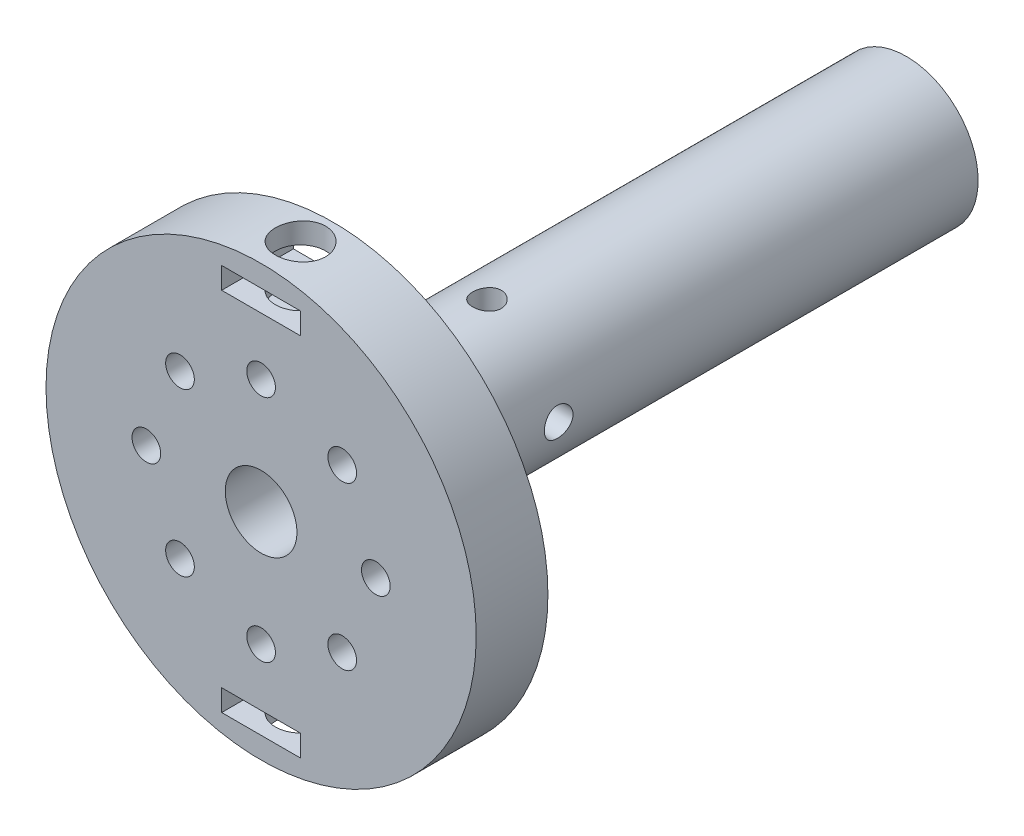
SolidWorks part; units mm, degrees
ref_plane "Front Plane" through (0, 0, 0) normal (0, 0, 1) x (1, 0, 0)
ref_plane "Top Plane" through (0, 0, 0) normal (0, 1, 0) x (1, 0, 0)
ref_plane "Right Plane" through (0, 0, 0) normal (1, 0, 0) x (0, 0, -1)
sketch "Sketch1" plane through (0, 0, 0) normal (0, 0, 1) x (1, 0, 0)
  circle A0 centre (0, 0) radius 30
  dimension "D1" = 60
extrude "Boss-Extrude1" add sketch "Sketch1" along normal blind 10
sketch "Sketch2" plane through (0, 0, 0) normal (0, 0, -1) x (-1, 0, 0)
  circle A0 centre (0, 0) radius 10
  dimension "D1" = 20
extrude "Boss-Extrude2" add sketch "Sketch2" along normal blind 80
extrude "Boss-Extrude3" add sketch "Sketch2<2>" along normal blind 20
sketch "Sketch2<2>" plane through (0, 0, 0) normal (0, 0, -1) x (-1, 0, 0) same geometry as "Sketch2"
sketch "Sketch5" plane through (0, 0, -80) normal (0, 0, -1) x (-1, 0, 0)
  circle A0 centre (0, 0) radius 5
  dimension "D1" = 10
extrude "Cut-Extrude1" cut sketch "Sketch5" against normal through all
sketch "Sketch6" plane through (0, 0, 0) normal (0, 1, 0) x (1, 0, 0)
  line L1 (30, 0) -> (-30, 0) construction
  circle A0 centre (0, 21.5) radius 2
  dimension "D1" = 4
  dimension "D2" = 21.5
extrude "Cut-Extrude2" cut sketch "Sketch6" against normal through all both and the other way through all
pattern_circular "CirPattern1" count 2 over 90 about axis through (0, 0, -80) along (0, 0, 1) of "Cut-Extrude2"
sketch "Sketch7" plane through (0, 0, 10) normal (0, 0, 1) x (1, 0, 0)
  circle A0 centre (0, 16) radius 2
  circle A1 centre (11.3137, 11.3137) radius 2
  circle A2 centre (16, 0) radius 2
  circle A3 centre (11.3137, -11.3137) radius 2
  circle A4 centre (0, -16) radius 2
  circle A5 centre (-11.3137, -11.3137) radius 2
  circle A6 centre (-16, 0) radius 2
  circle A7 centre (-11.3137, 11.3137) radius 2
  point P20 (0, 0)
  dimension "D1" = 4
  dimension "D2" = 16
  dimension "D3" = 8
extrude "Cut-Extrude3" cut sketch "Sketch7" against normal through all and the other way through all
sketch "Sketch9" plane through (0, 0, 0) normal (0, 0, -1) x (-1, 0, 0)
  line L0 (0, 0) -> (0, 30) construction
  line L3 (-5.5, 24) -> (5.5, 24)
  line L4 (-5.5, 24) -> (-5.5, 27)
  line L5 (-5.5, 27) -> (5.5, 27)
  line L6 (5.5, 24) -> (5.5, 27)
  line L7 (-5.5, 24) -> (5.5, 27) construction
  line L8 (-5.5, 27) -> (5.5, 24) construction
  circle A0 centre (0, 0) radius 30 construction
  point P6 (0, 25.5)
  dimension "D1" = 11
  dimension "D2" = 3
  dimension "D3" = 24
extrude "Cut-Extrude5" cut sketch "Sketch9" against normal blind 10
mirror "Mirror1" about plane through (0, 0, 0) normal (0, 1, 0) of "Cut-Extrude5"
ref_plane "Plane1" through (0, -30, 0) normal (0, -1, 0) x (-1, 0, 0)
sketch "Sketch10" plane through (0, -30, 0) normal (0, -1, 0) x (-1, 0, 0)
  line L1 (0, -1) -> (1.1394, -1) construction
  line L2 (30, 0) -> (-30, 0) construction
  circle A0 centre (0, -4.5) radius 3.5
  dimension "D1" = 7
  dimension "D2" = 1
  dimension "D3" = 3.5
extrude "Cut-Extrude6" cut sketch "Sketch10" against normal blind 8
mirror "Mirror2" about plane through (0, 0, 0) normal (0, 1, 0) of "Cut-Extrude6"
sketch "Sketch15" plane through (0, 0, 0) normal (0, 1, 0) x (1, 0, 0)
  line L0 (-30.0139, 55) -> (35.3147, 55) construction
  line L1 (10, 80) -> (-10, 80) construction
  dimension "D1" = 25
ref_plane "Plane3" through (0, 0, -55) normal (0, 0, -1) x (-1, 0, 0)
sketch "Sketch17" plane through (0, 0, -55) normal (0, 0, -1) x (-1, 0, 0)
  circle A0 centre (0, 0) radius 7.3556
extrude "Boss-Extrude4" add sketch "Sketch17" along normal blind 25
sketch "Sketch18" plane through (0, 0, -80) normal (0, 0, -1) x (-1, 0, 0)
  circle A0 centre (0, 0) radius 2
  dimension "D1" = 4
extrude "Cut-Extrude7" cut sketch "Sketch18" against normal blind 10
